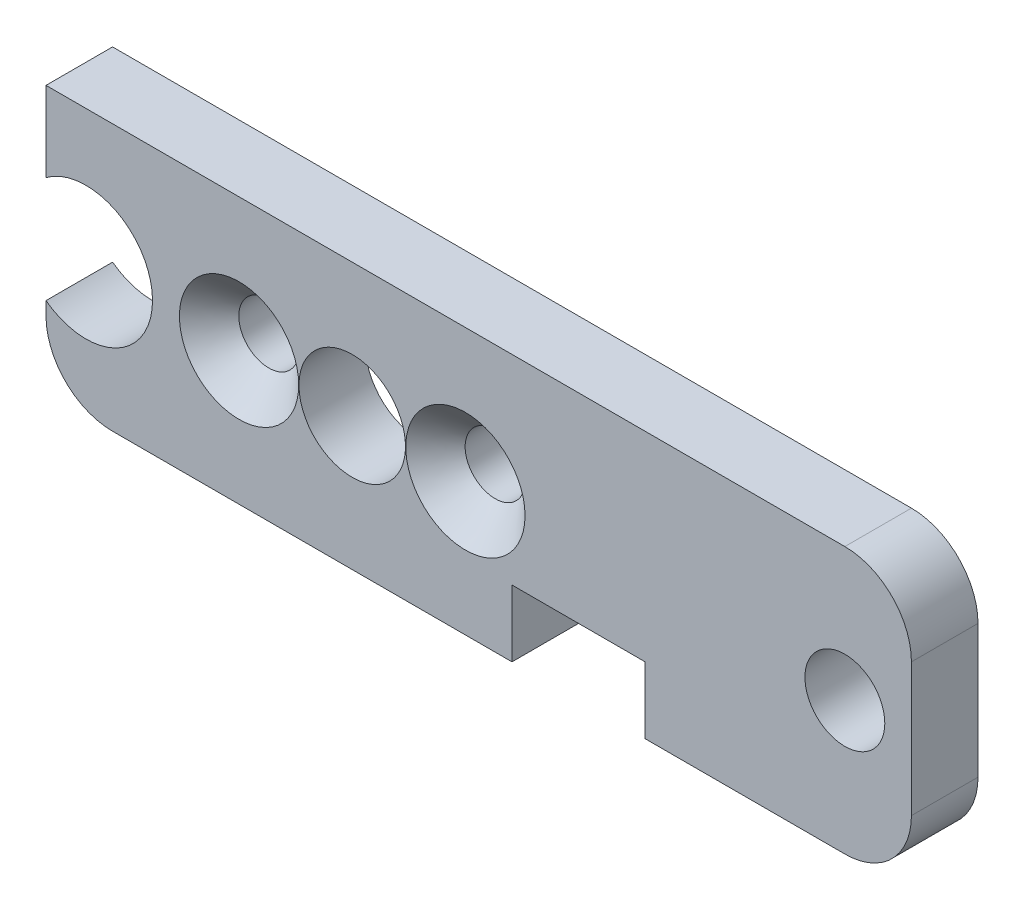
SolidWorks part; units mm, degrees
ref_plane "Front Plane" through (0, 0, 0) normal (0, 0, 1) x (1, 0, 0)
ref_plane "Top Plane" through (0, 0, 0) normal (0, 1, 0) x (1, 0, 0)
ref_plane "Right Plane" through (0, 0, 0) normal (1, 0, 0) x (0, 0, -1)
sketch "Sketch1" plane through (0, 0, 0) normal (0, 0, 1) x (1, 0, 0)
  line L1 (-27.303, 7.4194) -> (37.697, 7.4194)
  line L2 (-27.303, 7.4194) -> (-27.303, -12.5806)
  line L3 (-27.303, -12.5806) -> (37.697, -12.5806)
  line L4 (37.697, 7.4194) -> (37.697, -12.5806)
  dimension "D1" = 65
  dimension "D2" = 20
extrude "Boss-Extrude1" add sketch "Sketch1" along normal blind 5
sketch "Sketch2" plane through (0, 0, 5) normal (0, 0, 1) x (1, 0, 0)
  line L0 (-24.303, -2.5806) -> (-4.303, -2.5806) construction
  line L1 (-27.303, 7.4194) -> (-27.303, -12.5806) construction
  line L2 (-4.303, -2.5806) -> (-10.3134, -8.591) construction
  line L3 (-27.303, -2.5806) -> (-24.303, -2.5806) construction
  line L4 (-4.303, -2.5806) -> (-12.803, -2.5806) construction
  line L5 (-4.303, -2.5806) -> (1.7074, 3.4298) construction
  line L6 (-4.303, -2.5806) -> (4.197, -2.5806) construction
  line L7 (37.697, -2.5806) -> (32.697, -2.5806) construction
  line L8 (37.697, -12.5806) -> (37.697, 7.4194) construction
  dimension "D6" = 8.5
  dimension "D1" = 3
  dimension "D2" = 20
  dimension "D3" = 8.5
  dimension "D4" = 8.5
  dimension "D5" = 8.5
  dimension "D7" = 5
hole_wizard "Ø10.0mm Dowel Hole1" positions "3DSketch2" profile "Sketch4" hole size "Ø10.0" standard "ISO"
sketch3d "3DSketch2"
  point P0 (-24.303, -2.5806, 5)
sketch "Sketch4" plane through (-24.303, -2.5806, 5) normal (1, 0, 0) x (0, -1, 0)
  line L0 (0, 0) -> (0, 28.0043)
  line L1 (0, 28.0043) -> (5, 25)
  line L2 (5, 25) -> (5, 0)
  line L5 (5, 0) -> (0, 0)
  line L10 (0, 28.0043) -> (-5, 25) construction
  line L11 (0, -6.35) -> (0, 107.95) construction
  dimension "Hole Dia." = 10
  dimension "Hole Depth" = 25
  dimension "Drill Angle" = 118
hole_wizard "CSK for M4 Hex Socket Countersunk Cap Screw1" positions "3DSketch5" profile "Sketch8" countersink size "M4" standard "ISO" end condition through all
sketch3d "3DSketch5"
  point P0 (-12.803, -2.5806, 5)
  point P3 (4.197, -2.5806, 5)
sketch "Sketch8" plane through (-12.803, -2.5806, 5) normal (1, 0, 0) x (0, -1, 0)
  line L0 (0, 0) -> (0, 5)
  line L1 (0, 5) -> (2.25, 5)
  line L2 (2.25, 5) -> (2.25, 2.23)
  line L3 (2.25, 2.23) -> (4.48, 0)
  line L5 (4.48, 0) -> (0, 0)
  line L6 (-2.25, 2.23) -> (-4.48, 0) construction
  line L11 (0, -6.35) -> (0, 107.95) construction
  dimension "Thru Hole Dia." = 4.5
  dimension "Thru Hole Depth" = 5
  dimension "Near C'Sink Dia." = 8.96
  dimension "Near C'Sink Angle" = 90
hole_wizard "Ø6.0mm Dowel Hole1" positions "3DSketch6" profile "Sketch9" hole size "Ø6.0" standard "ISO"
sketch3d "3DSketch6"
  point P0 (32.697, -2.5806, 5)
sketch "Sketch9" plane through (32.697, -2.5806, 5) normal (1, 0, 0) x (0, -1, 0)
  line L0 (0, 0) -> (0, 26.8026)
  line L1 (0, 26.8026) -> (3, 25)
  line L2 (3, 25) -> (3, 0)
  line L5 (3, 0) -> (0, 0)
  line L10 (0, 26.8026) -> (-3, 25) construction
  line L11 (0, -6.35) -> (0, 107.95) construction
  dimension "Hole Dia." = 6
  dimension "Hole Depth" = 25
  dimension "Drill Angle" = 118
sketch "Sketch11" plane through (0, 0, 0) normal (0, 0, -1) x (-1, 0, 0)
  line L0 (4.303, -2.5806) -> (4.303, -6.9847) construction
hole_wizard "Ø4.0mm Dowel Hole2" positions "3DSketch8" profile "Sketch13" hole size "Ø4.0" standard "ISO"
sketch3d "3DSketch8"
  point P0 (-4.303, -2.5806, 0)
sketch "Sketch13" plane through (-4.303, -2.5806, 0) normal (1, 0, 0) x (0, 1, 0)
  line L0 (0, 0) -> (0, 26.2017)
  line L1 (0, 26.2017) -> (2, 25)
  line L2 (2, 25) -> (2, 0)
  line L5 (2, 0) -> (0, 0)
  line L10 (0, 26.2017) -> (-2, 25) construction
  line L11 (0, -6.35) -> (0, 107.95) construction
  dimension "Hole Dia." = 4
  dimension "Hole Depth" = 25
  dimension "Drill Angle" = 118
hole_wizard "Ø8.0mm Dowel Hole1" positions "3DSketch9" profile "Sketch14" hole size "Ø8.0" standard "ISO"
sketch3d "3DSketch9"
  point P0 (-4.303, -2.5806, 0)
sketch "Sketch14" plane through (-4.303, -2.5806, 0) normal (1, 0, 0) x (0, 1, 0)
  line L0 (0, 0) -> (0, 7.4034)
  line L1 (0, 7.4034) -> (4, 5)
  line L2 (4, 5) -> (4, 0)
  line L5 (4, 0) -> (0, 0)
  line L10 (0, 7.4034) -> (-4, 5) construction
  line L11 (0, -6.35) -> (0, 107.95) construction
  dimension "Hole Dia." = 8
  dimension "Hole Depth" = 5
  dimension "Drill Angle" = 118
sketch "Sketch22" plane through (0, 0, 0) normal (0, 0, -1) x (-1, 0, 0)
  line L0 (-37.697, -2.5806) -> (-17.697, -2.5806) construction
  line L1 (-17.697, -2.5806) -> (-17.697, -12.5806) construction
  line L2 (27.303, -12.5806) -> (-37.697, -12.5806) construction
  line L3 (-17.697, -12.5806) -> (-17.697, -7.5806)
  line L4 (-17.697, -7.5806) -> (-7.697, -7.5806)
  line L5 (-7.697, -7.5806) -> (-7.697, -12.5806)
  line L6 (-7.697, -12.5806) -> (-17.697, -12.5806)
  dimension "D1" = 20
  dimension "D2" = 5
  dimension "D3" = 10
extrude "Cut-Extrude1" cut sketch "Sketch22" against normal blind 10
sketch "Sketch23" plane through (0, 0, 0) normal (0, 0, -1) x (-1, 0, 0)
  circle A0 centre (4.303, -2.5806) radius 12.5
  circle A1 centre (24.303, -2.5806) radius 5
  dimension "D1" = 25
  dimension "D2" = 10
sketch "Sketch25" plane through (0, -7.5806, 0) normal (0, -1, 0) x (1, 0, 0)
  line L0 (17.697, 2.5) -> (7.697, 2.5) construction
  line L1 (17.697, 5) -> (17.697, 0) construction
  line L2 (7.697, 5) -> (7.697, 0) construction
  line L3 (12.697, 2.5) -> (12.697, 5) construction
  line L4 (17.697, 5) -> (7.697, 5) construction
hole_wizard "M2 Tapped Hole2" positions "3DSketch12" profile "Sketch26" tap size "M2" standard "ISO"
sketch3d "3DSketch12"
  point P0 (12.697, -7.5806, 2.5)
sketch "Sketch26" plane through (12.697, -7.5806, 2.5) normal (1, 0, 0) x (0, 0, -1)
  line L0 (0, 0) -> (0, 7.4807)
  line L1 (0, 7.4807) -> (0.8, 7)
  line L2 (0.8, 7) -> (0.8, 0)
  line L5 (0.8, 0) -> (0, 0)
  line L10 (0, 7.4807) -> (-0.8, 7) construction
  line L11 (0, -6.35) -> (0, 107.95) construction
  dimension "Tap Drill Dia." = 1.6
  dimension "Tap Drill Depth" = 7
  dimension "Drill Angle" = 118
cosmetic thread "Hole Thread1" parameters "D1"=5, "D2"=2
fillet "Fillet1" radius 5 3 edges at (37.697, 7.4194, 2.5) (37.697, -12.5806, 2.5) (-27.303, -12.5806, 2.5)
